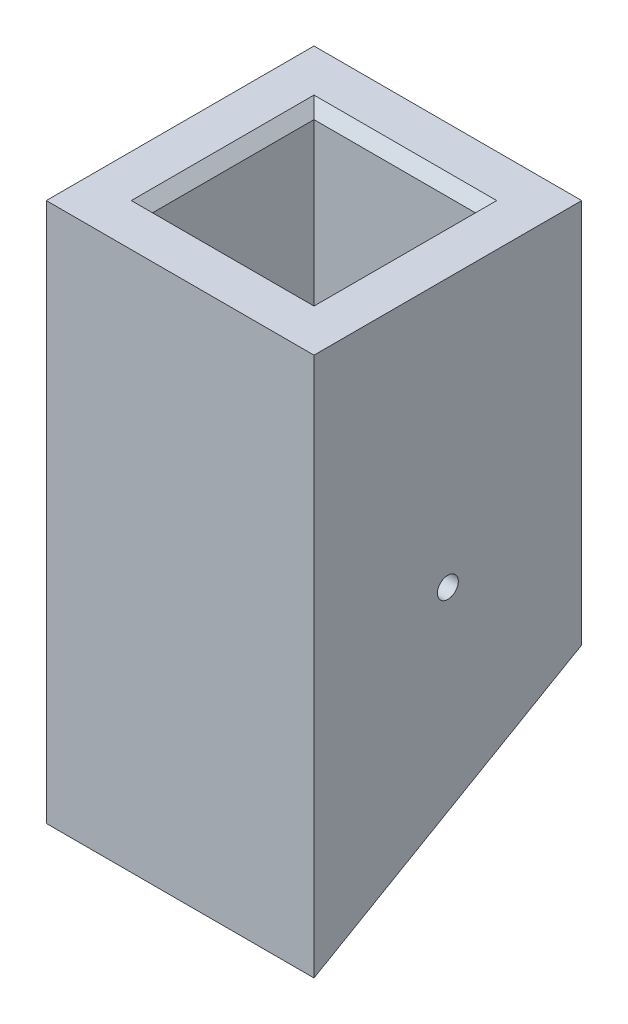
SolidWorks part; units mm, degrees
ref_plane "Front Plane" through (0, 0, 0) normal (0, 0, 1) x (1, 0, 0)
ref_plane "Top Plane" through (0, 0, 0) normal (0, 1, 0) x (1, 0, 0)
ref_plane "Right Plane" through (0, 0, 0) normal (1, 0, 0) x (0, 0, -1)
sketch "Sketch1" plane through (0, 0, 0) normal (0, 1, 0) x (1, 0, 0)
  line L0 (-16.002, 16.002) -> (-16.002, -16.002)
  line L1 (-9.652, 9.652) -> (9.652, 9.652)
  line L2 (-9.652, 9.652) -> (-9.652, -9.652)
  line L3 (-9.652, -9.652) -> (9.652, -9.652)
  line L4 (9.652, 9.652) -> (9.652, -9.652)
  line L5 (-9.652, 9.652) -> (9.652, -9.652) construction
  line L6 (-9.652, -9.652) -> (9.652, 9.652) construction
  line L7 (-16.002, -16.002) -> (16.002, -16.002)
  line L8 (16.002, 16.002) -> (16.002, -16.002)
  line L9 (-16.002, 16.002) -> (16.002, 16.002)
  point P0 (0, 0)
  dimension "D1" = 19.304
  dimension "D2" = 6.35
extrude "Boss-Extrude1" add sketch "Sketch1" along normal blind 57.15 contours L9 L0 L7 L8 L1 L4 L3 L2 region at (0, 0, -15.5494)
sketch "Sketch2" plane through (16.002, 0, 0) normal (1, 0, 0) x (0, 0, -1)
  line L0 (-16.002, 0) -> (16.002, 18.4775)
  line L1 (16.002, 57.15) -> (16.002, 0) construction
  line L2 (16.002, 0) -> (-16.002, 0) construction
  line M2 (-16.002, 0) -> (16.002, 0)
  line M3 (16.002, 0) -> (16.002, 57.15)
  dimension "D1" = 30
extrude "Cut-Extrude1" cut sketch "Sketch2" against normal blind 57.15 and the other way through all contours L0 M2 M3 region at (16.002, 6.1592, -5.334)
sketch "Sketch3" plane through (16.002, 0, 0) normal (1, 0, 0) x (0, 0, -1)
  line L0 (0, 9.2388) -> (0, 25.1138) construction
  line L1 (16.002, 18.4775) -> (-16.002, 0) construction
  circle A0 centre (0, 25.1138) radius 1.25
  dimension "D2" = 2.5
  dimension "D1" = 15.875
extrude "Cut-Extrude2" cut sketch "Sketch3" against normal blind 57.15
sketch "Sketch5" plane through (16.002, 0, 0) normal (1, 0, 0) x (0, 0, -1)
  line L0 (-16.002, -7.3323) -> (16.002, 11.1452)
  line L1 (16.002, 11.1452) -> (16.002, 18.4775)
  line L2 (-16.002, 0) -> (-16.002, -7.3323)
  line L3 (16.002, 18.4775) -> (-16.002, 0) construction
  line L8 (-16.002, 0) -> (16.002, 18.4775)
  line L9 (16.002, 18.4775) -> (16.002, 57.15)
  line L10 (16.002, 57.15) -> (-16.002, 57.15)
  line L11 (-16.002, 57.15) -> (-16.002, 0)
  line L12 (-16.002, 0) -> (16.002, 18.4775)
  point P7 (-15.5795, -3.2993)
  point P9 (-15.875, 0)
  dimension "D1" = 6.35
  dimension "D2" = 0
extrude "Boss-Extrude3" add sketch "Sketch5" against normal up to surface (32.004 mm away) up to face at (-16.002, 25.1138, -1.25)
chamfer "Chamfer1" distance 1.27 angle 45 4 edges at (9.652, 57.15, 0) (0, 57.15, 9.652) (-9.652, 57.15, 0) (0, 57.15, -9.652)
